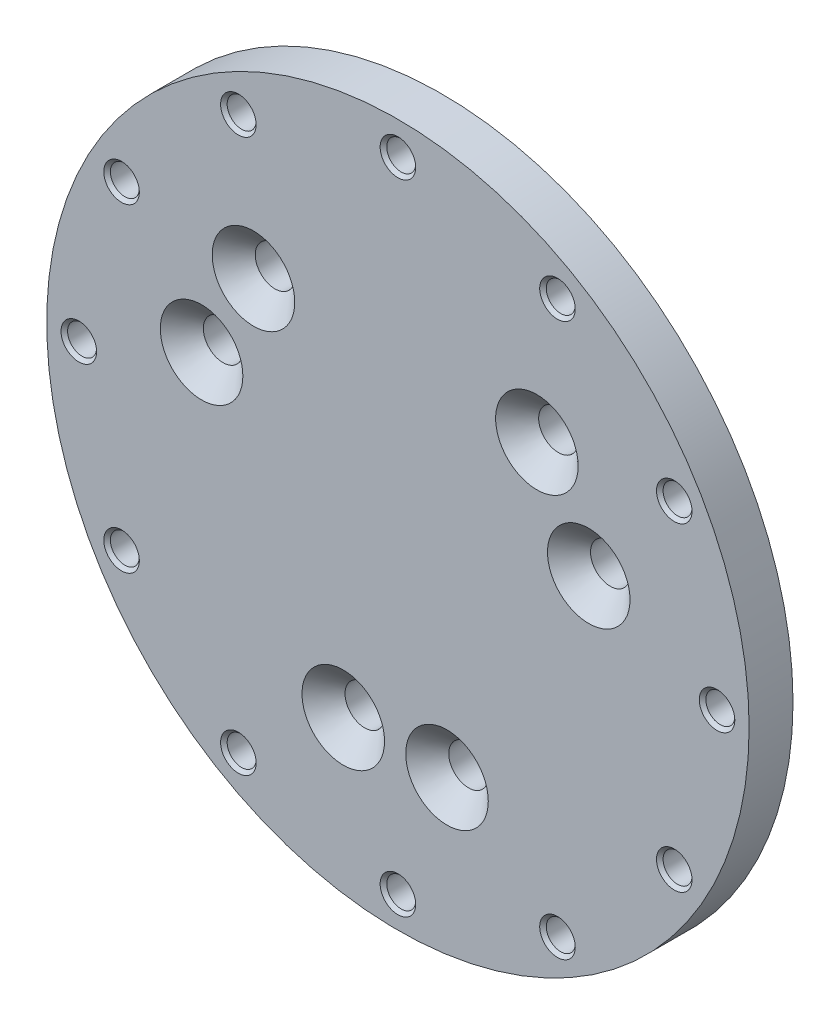
SolidWorks part; units mm, degrees
ref_plane "Front Plane" through (0, 0, 0) normal (0, 0, 1) x (1, 0, 0)
ref_plane "Top Plane" through (0, 0, 0) normal (0, 1, 0) x (1, 0, 0)
ref_plane "Right Plane" through (0, 0, 0) normal (1, 0, 0) x (0, 0, -1)
sketch "Sketch1" plane through (0, 0, 0) normal (0, 0, 1) x (1, 0, 0)
  circle A0 centre (0, 0) radius 27.5
  dimension "D1" = 55
extrude "Boss-Extrude1" add sketch "Sketch1" along normal mid plane 8 contours A0
sketch "Sketch2" plane through (0, 0, 4) normal (0, 0, 1) x (1, 0, 0)
  circle A0 centre (0, 0) radius 40
  dimension "D1" = 80
extrude "Boss-Extrude2" add sketch "Sketch2" along normal blind 5
sketch "Sketch3" plane through (0, 0, 9) normal (0, 0, 1) x (1, 0, 0)
  line L0 (0, 0) -> (36.25, 0) construction
  line L1 (0, 0) -> (21.7333, 5.8234) construction
  line L2 (0, 0) -> (0, 36.25) construction
  circle A0 centre (0, 0) radius 36.25 construction
  circle A1 centre (0, 0) radius 22.5 construction
  dimension "D1" = 72.5
  dimension "D2" = 45
  dimension "D3" = 15
hole_wizard "M4x0.7 Tapped Hole1" positions "Sketch4" profile "Sketch5" tap size "M4x0.7" standard "ANSI Metric"
sketch "Sketch4" plane through (0, 0, 9) normal (0, 0, 1) x (1, 0, 0)
  point P5 (0, 36.25)
sketch "Sketch5" plane through (0, 36.25, 9) normal (1, 0, 0) x (0, -1, 0)
  line L0 (0, 0) -> (0, 11.0914)
  line L1 (0, 11.0914) -> (1.65, 10.1)
  line L2 (1.65, 10.1) -> (1.65, 0.375)
  line L3 (1.65, 0.375) -> (2.025, 0)
  line L5 (2.025, 0) -> (0, 0)
  line L6 (-1.65, 0.375) -> (-2.025, 0) construction
  line L10 (0, 11.0914) -> (-1.65, 10.1) construction
  line L11 (0, -6.35) -> (0, 107.95) construction
  dimension "Tap Drill Dia." = 3.3
  dimension "Tap Drill Depth" = 10.1
  dimension "Near C'Sink Dia." = 4.05
  dimension "Near C'Sink Angle" = 90
  dimension "Drill Angle" = 118
cosmetic thread "Hole Thread1" parameters "D1"=8, "D2"=4
pattern_circular "CirPattern1" count 12 over 360 about axis through (0, -0.0931, 0) along (0, 0, 1) of "M4x0.7 Tapped Hole1"
cosmetic thread "Hole Thread2" parameters "D1"=8, "D2"=4
cosmetic thread "Hole Thread3" parameters "D1"=8, "D2"=4
cosmetic thread "Hole Thread4" parameters "D1"=8, "D2"=4
cosmetic thread "Hole Thread5" parameters "D1"=8, "D2"=4
cosmetic thread "Hole Thread6" parameters "D1"=8, "D2"=4
cosmetic thread "Hole Thread7" parameters "D1"=8, "D2"=4
cosmetic thread "Hole Thread8" parameters "D1"=8, "D2"=4
cosmetic thread "Hole Thread9" parameters "D1"=8, "D2"=4
cosmetic thread "Hole Thread10" parameters "D1"=8, "D2"=4
cosmetic thread "Hole Thread11" parameters "D1"=8, "D2"=4
cosmetic thread "Hole Thread12" parameters "D1"=8, "D2"=4
hole_wizard "CSK for M4 Flat Head Machine Screw2" positions "Sketch13" profile "Sketch14" countersink size "M4" standard "ANSI Metric"
sketch "Sketch13" plane through (0, 0, 9) normal (0, 0, 1) x (1, 0, 0)
  point P0 (21.7333, 5.8234)
sketch "Sketch14" plane through (21.7333, 5.8234, 9) normal (1, 0, 0) x (0, -1, 0)
  line L0 (0, 0) -> (0, 14.3509)
  line L1 (0, 14.3509) -> (2.25, 12.999)
  line L2 (2.25, 12.999) -> (2.25, 2.45)
  line L3 (2.25, 2.45) -> (4.7, 0)
  line L5 (4.7, 0) -> (0, 0)
  line L6 (-2.25, 2.45) -> (-4.7, 0) construction
  line L10 (0, 14.3509) -> (-2.25, 12.999) construction
  line L11 (0, -6.35) -> (0, 107.95) construction
  dimension "Hole Dia." = 4.5
  dimension "Hole Depth" = 12.999
  dimension "Near C'Sink Dia." = 9.4
  dimension "Near C'Sink Angle" = 90
  dimension "Drill Angle" = 118
pattern_circular "CirPattern3" count 12 over 360 about axis through (-0.3141, -0.0812, 0) along (0, 0, 1) skipping 2, 3, 6, 7, 10, 11 of "CSK for M4 Flat Head Machine Screw2"
fillet "Fillet2" radius 10 1 edges at (27.5, 0, 4)
